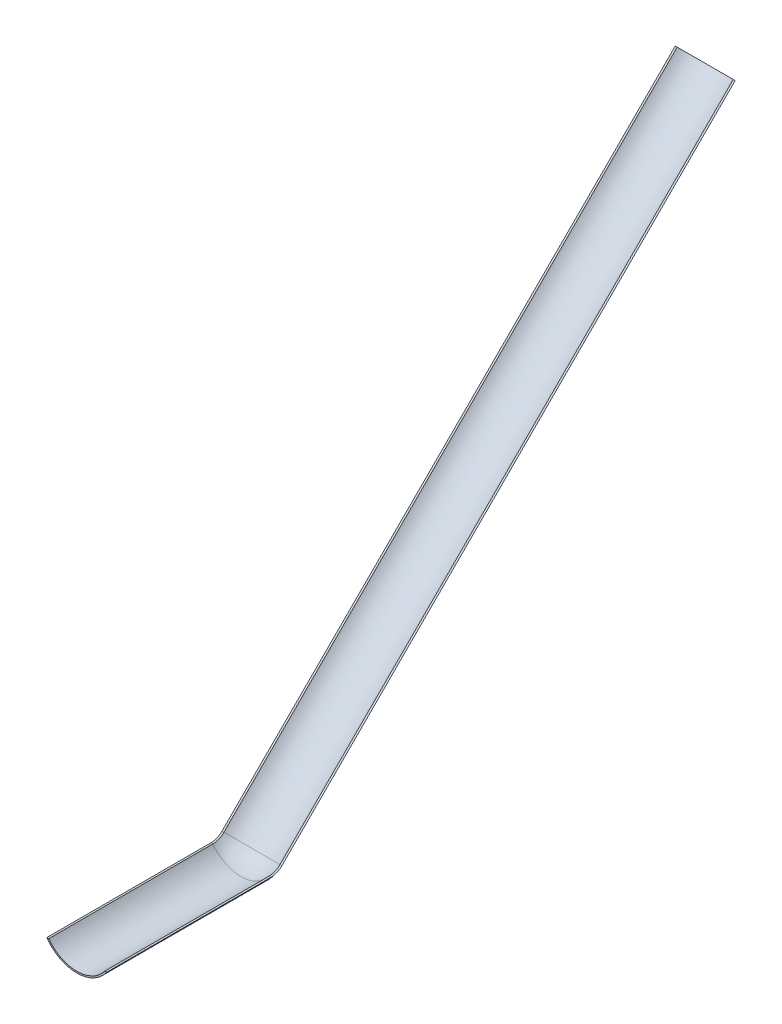
SolidWorks part; units mm, degrees
ref_plane "Front Plane" through (0, 0, 0) normal (0, 0, 1) x (1, 0, 0)
ref_plane "Top Plane" through (0, 0, 0) normal (0, 1, 0) x (1, 0, 0)
ref_plane "Right Plane" through (0, 0, 0) normal (1, 0, 0) x (0, 0, -1)
sketch "Sketch1" plane through (0, 0, 0) normal (1, 0, 0) x (0, 0, -1)
  line L0 (52, 0) -> (0, 0)
  line L1 (202.7552, 146.613) -> (59.0711, 2.9289)
  arc A0 (59.0711, 2.9289) -> (52, 0) centre (52, 10) cw
  point P0 (0, 0)
  dimension "D3" = 10
  dimension "D1" = 52
  dimension "D2" = 203.2
  dimension "D4" = 45
sketch "Sketch2" plane through (0, 0, 0) normal (0, 0, 1) x (1, 0, 0)
  line L0 (-9.5, 5) -> (-8.8868, 5)
  line L1 (8.8868, 5) -> (9.5, 5)
  arc A0 (-9.5, 5) -> (9.5, 5) centre (0, 11.525) ccw
  arc A1 (-8.8868, 5) -> (8.8868, 5) centre (0, 11.525) ccw
  circle A3 centre (0, 11.525) radius 11.025 construction
  circle A4 centre (0, 11.525) radius 11.525 construction
  point P3 (5.1674, 71.3453)
  point P10 (4.6892, 71.1992)
  dimension "D2" = 5
  dimension "D3" = 19
  dimension "D1" = 0.5
sweep "Sweep1" add profiles "Sketch2" path "Sketch1"
sketch "Sketch3" [suppressed] plane through (0, 0, 0) normal (1, 0, 0) x (0, 0, -1)
  line L0 (52, 0) -> (0, 0) construction
  line L1 (202.7552, 146.613) -> (59.0711, 2.9289) construction
  line L2 (52, 0) -> (0, 0)
  line L3 (202.7552, 146.613) -> (59.0711, 2.9289)
  arc A0 (52, 0) -> (59.0711, 2.9289) centre (52, 10) ccw construction
  arc A1 (52, 0) -> (59.0711, 2.9289) centre (52, 10) ccw
sketch "Sketch4" [suppressed] plane through (0, 0, 0) normal (0, 0, 1) x (1, 0, 0)
  line L1 (-11.165, 0.5) -> (11.165, 0.5)
  line L2 (-11.165, 0.5) -> (-11.165, 0)
  line L3 (-11.165, 0) -> (11.165, 0)
  line L4 (11.165, 0.5) -> (11.165, 0)
  point P4 (0, 0)
  dimension "D1" = 0.5
  dimension "D2" = 22.33
sweep "Sweep2" [suppressed] add profiles "Sketch4" path "Sketch3"
